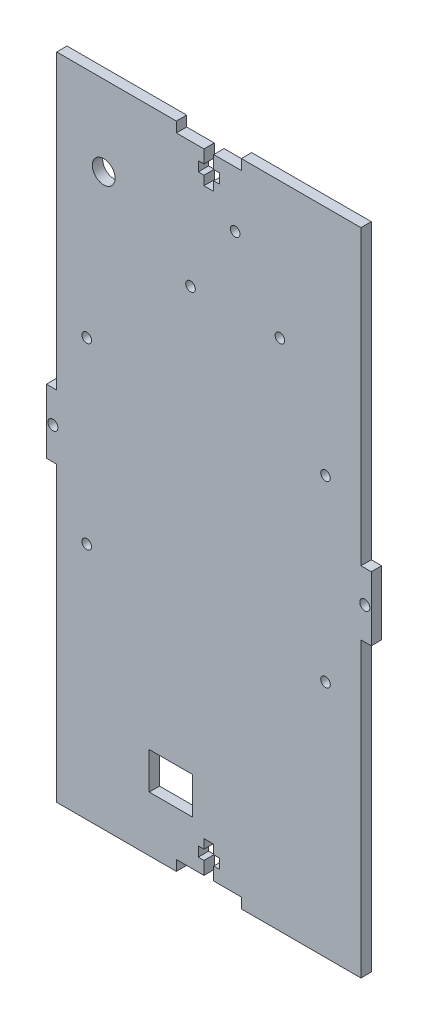
SolidWorks part; units mm, degrees
ref_plane "Front Plane" through (0, 0, 0) normal (0, 0, 1) x (1, 0, 0)
ref_plane "Top Plane" through (0, 0, 0) normal (0, 1, 0) x (1, 0, 0)
ref_plane "Right Plane" through (0, 0, 0) normal (1, 0, 0) x (0, 0, -1)
sketch "Sketch1" plane through (0, 0, 0) normal (0, 0, 1) x (1, 0, 0)
  line L0 (0, 40) -> (0, -40) construction
  line L5 (-50, -100) -> (50, 100) construction
  line L6 (-50, 100) -> (50, -100) construction
  line L7 (-100, 0) -> (100, 0) construction
  line L32 (-50, 100) -> (50, 100)
  line L35 (50, 100) -> (50, -100)
  line L36 (50, -100) -> (-50, -100)
  line L37 (-50, -100) -> (-50, 100)
  point P0 (0, 0)
  dimension "D1" = 100
  dimension "D2" = 200
extrude "Boss-Extrude2" add sketch "Sketch1" along normal blind 3.18
sketch "Sketch2" plane through (0, 0, 3.18) normal (0, 0, 1) x (1, 0, 0)
  line L0 (0, -100) -> (0, 100) construction
  line L1 (-123.0225, 0) -> (147.0753, 0) construction
  line L2 (50, 100) -> (-50, 100) construction
  line L4 (-10, 100) -> (-10, 96.82)
  line L5 (-10, 96.82) -> (-1.5, 96.82)
  line L6 (10, 100) -> (10, 96.82)
  line L7 (1.5, 96.82) -> (10, 96.82)
  line L9 (-1.5, 96.82) -> (-1.5, 92.82)
  line L10 (-1.5, 87) -> (1.5, 87)
  line L11 (1.5, 96.82) -> (1.5, 92.82)
  line L12 (-3.25, 92.82) -> (-1.5, 92.82)
  line L13 (-3.25, 92.82) -> (-3.25, 89.82)
  line L14 (-3.25, 89.82) -> (-1.5, 89.82)
  line L15 (3.25, 92.82) -> (3.25, 89.82)
  line L16 (1.5, 92.82) -> (3.25, 92.82)
  line L17 (-1.5, 89.82) -> (-1.5, 87)
  line L18 (1.5, 89.82) -> (1.5, 87)
  line L19 (1.5, 89.82) -> (3.25, 89.82)
  line L20 (-10, 100) -> (10, 100)
  line L21 (-50, -100) -> (50, -100) construction
  line L22 (-50, 100) -> (-50, -100) construction
  line L23 (-50, 9.875) -> (-46.82, 9.875)
  line L24 (-50, 9.875) -> (-50, 100)
  line L25 (-50, 100) -> (-46.82, 100)
  line L26 (-46.82, 9.875) -> (-46.82, 100)
  line L28 (-50, -9.875) -> (-46.82, -9.875)
  line L29 (-50, -9.875) -> (-50, -100)
  line L30 (-50, -100) -> (-46.82, -100)
  line L31 (-46.82, -9.875) -> (-46.82, -100)
  circle A0 centre (-48, 0) radius 1.55
  dimension "D11" = 3.1
  dimension "D12" = 2
  dimension "D1" = 4
  dimension "D2" = 3
  dimension "D3" = 3
  dimension "D4" = 20
  dimension "D5" = 6.5
  dimension "D6" = 3.18
  dimension "D7" = 13
  dimension "D8" = 19.75
  dimension "D9" = 3.18
  dimension "D10" = 3.18
extrude "Cut-Extrude1" cut sketch "Sketch2" against normal through all
mirror "Mirror1" about plane through (0, 0, 0) normal (0, 1, 0) of "Cut-Extrude1"
mirror "Mirror3" about plane through (0, 0, 0) normal (1, 0, 0) of "Cut-Extrude1"
sketch "Sketch4" plane through (0, 0, 3.18) normal (0, 0, 1) x (1, 0, 0)
  line L5 (-18.3522, -83.0261) -> (-5.0022, -83.0261)
  line L6 (-18.3522, -83.0261) -> (-18.3522, -71.6761)
  line L7 (-18.3522, -71.6761) -> (-5.0022, -71.6761)
  line L8 (-5.0022, -83.0261) -> (-5.0022, -71.6761)
  dimension "D1" = 13.35
  dimension "D2" = 11.35
sketch "Sketch5" plane through (0, 0, 3.18) normal (0, 0, 1) x (1, 0, 0)
  circle A0 centre (-37.5809, 28.4641) radius 1.47
  circle A1 centre (35.9045, 28.4641) radius 1.47
  circle A2 centre (-37.5809, -26.5359) radius 1.47
  circle A3 centre (35.9045, -26.5359) radius 1.47
  circle A4 centre (-37.5809, 28.4641) radius 1.47 construction
  circle A5 centre (35.9045, 28.4641) radius 1.47 construction
  circle A6 centre (35.9045, -26.5359) radius 1.47 construction
  circle A8 centre (-37.5809, -26.5359) radius 1.47 construction
extrude "Cut-Extrude4" cut sketch "Sketch5" against normal through all
sketch "Sketch6" plane through (0, 0, 3.18) normal (0, 0, 1) x (1, 0, 0)
  circle A0 centre (-5.6383, 58.12) radius 1.47
  circle A1 centre (8.1117, 79.62) radius 1.47
  circle A2 centre (21.8617, 58.12) radius 1.47
  circle A3 centre (-5.6383, 58.12) radius 1.4 construction
  circle A4 centre (8.1117, 79.62) radius 1.4 construction
  circle A5 centre (21.8617, 58.12) radius 1.4 construction
  dimension "D1" = 2.94
extrude "Cut-Extrude5" cut sketch "Sketch6" against normal through all
sketch "Sketch7" plane through (0, 0, 13.055) normal (0, 0, 1) x (1, 0, 0)
  circle A0 centre (-32.3543, 75.3033) radius 3.5
  circle A1 centre (-32.3543, 75.3033) radius 3.43 construction
  dimension "D1" = 7
extrude "Cut-Extrude6" cut sketch "Sketch7" against normal through all
extrude "Cut-Extrude7" cut sketch "Sketch4" against normal through all
